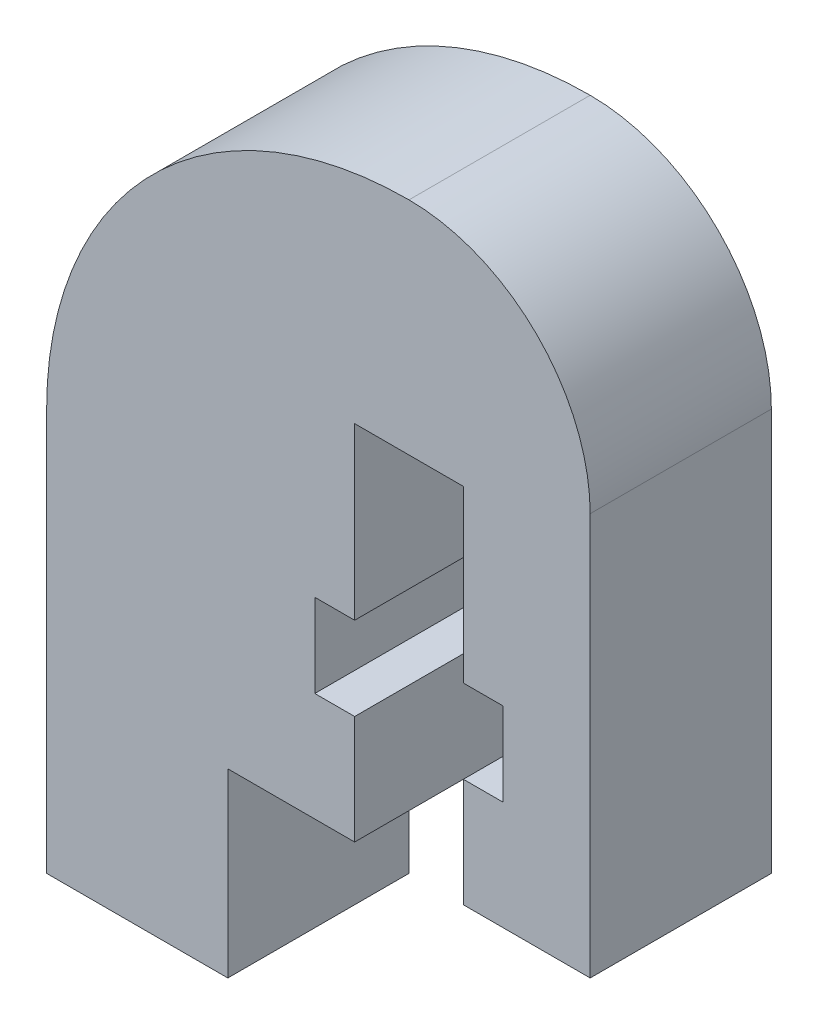
SolidWorks part; units mm, degrees
ref_plane "Front Plane" through (0, 0, 0) normal (0, 0, 1) x (1, 0, 0)
ref_plane "Top Plane" through (0, 0, 0) normal (0, 1, 0) x (1, 0, 0)
ref_plane "Right Plane" through (0, 0, 0) normal (1, 0, 0) x (0, 0, -1)
sketch "Sketch1" plane through (0, 0, 0) normal (0, 0, 1) x (1, 0, 0)
  line L0 (-16.9848, 5) -> (-16.9848, 16.2208) construction
  line L1 (-18.4848, 5) -> (-21.9848, 5)
  line L2 (-21.9848, 0) -> (-26.9848, 0)
  line L3 (-26.9848, 0) -> (-26.9848, 5)
  line L4 (-21.9848, 0) -> (-21.9848, 5)
  line L5 (-15.4848, 5) -> (-11.9848, 5)
  line L6 (-26.9848, 5) -> (-26.9848, 21.0974)
  line L7 (-11.9848, 5) -> (-11.9848, 21.0974)
  line L8 (-11.9848, 21.0974) -> (-26.9848, 21.0974)
  line L9 (-18.4848, 5) -> (-15.4848, 5) construction
  line L10 (-15.4848, 5) -> (-15.4848, 8)
  line L11 (-15.4848, 10.3) -> (-14.3848, 10.3)
  line L12 (-19.5848, 8) -> (-19.5848, 10.3)
  line L13 (-14.3848, 8) -> (-15.4848, 8)
  line L14 (-15.4848, 10.3) -> (-15.4848, 15)
  line L15 (-15.4848, 15) -> (-18.4848, 15)
  line L16 (-18.4848, 15) -> (-18.4848, 10.3)
  line L17 (-18.4848, 8) -> (-19.5848, 8)
  line L18 (-14.3848, 10.3) -> (-14.3848, 8)
  line L19 (-19.5848, 10.3) -> (-18.4848, 10.3)
  line L20 (-18.4848, 8) -> (-18.4848, 5)
  line L21 (-16.9848, 15) -> (-16.9848, 5) construction
  dimension "D1" = 5
  dimension "D2" = 5
  dimension "D3" = 5
  dimension "D4" = 5.2
  dimension "D5" = 3
  dimension "D6" = 2.3
  dimension "D7" = 3
  dimension "D8" = 10
extrude "Boss-Extrude1" add sketch "Sketch1" along normal blind 5
fillet "Fillet1" radius 10 1 edges at (-26.9848, 21.0974, 2.5)
fillet "Fillet2" radius 5 1 edges at (-11.9848, 21.0974, 2.5)
